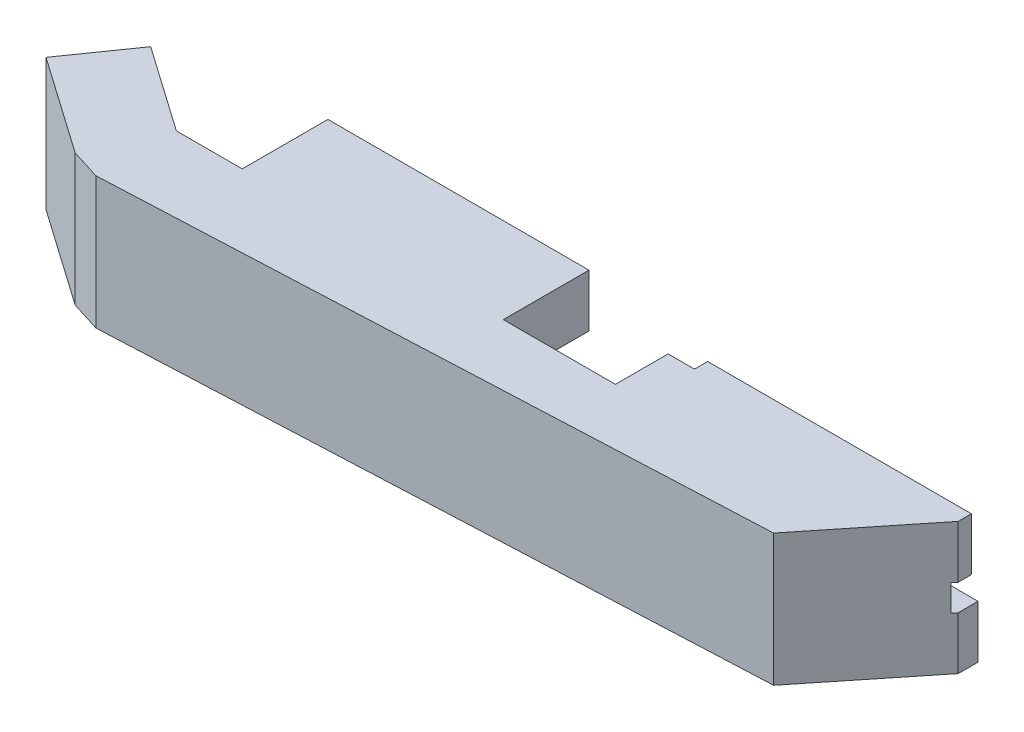
SolidWorks part; units mm, degrees
ref_plane "Front Plane" through (0, 0, 0) normal (0, 0, 1) x (1, 0, 0)
ref_plane "Top Plane" through (0, 0, 0) normal (0, 1, 0) x (1, 0, 0)
ref_plane "Right Plane" through (0, 0, 0) normal (1, 0, 0) x (0, 0, -1)
sketch "Sketch1" plane through (0, 0, 0) normal (0, 1, 0) x (1, 0, 0)
  line L0 (10.2515, 0) -> (39.2515, 0)
  line L1 (39.2515, 6) -> (47.2515, 6)
  line L6 (-8.1485, 0) -> (-15.5209, 5.1622)
  line L7 (-15.5209, 5.1622) -> (-15.693, 4.9164)
  line L11 (-0.0485, 0) -> (0.04, 0)
  line L12 (-8.1485, -0.3) -> (-8.2431, -0.3)
  line L13 (-15.693, 4.9164) -> (-8.2431, -0.3)
  line L14 (-8.1485, 0) -> (-8.245, -0.2987)
  line L18 (-15.693, 4.9164) -> (-14.5458, 6.5547)
  line L23 (-8.1485, 0) -> (-8.3206, -0.2457)
  line L24 (-14.5458, 6.5547) -> (-8.041, 2)
  line L25 (16.7515, 2) -> (25.2515, 2)
  line L26 (-3.0485, 2) -> (-8.041, 2)
  line L27 (-8.1485, 0) -> (-10.4428, -3.2766)
  line L28 (-15.5209, 5.1622) -> (-17.8152, 1.8856)
  line L29 (0.1927, 0) -> (10.0102, 0)
  line L30 (-0.0485, 0) -> (-3.0485, 0)
  line L31 (-3.0485, 2) -> (-3.0485, 8.5)
  line L32 (10.2515, 0) -> (16.7515, 0)
  line L33 (16.7515, 2) -> (16.7515, 8.5)
  line L34 (-3.0485, 8.5) -> (16.7515, 8.5)
  line L35 (27.2515, 6) -> (25.2515, 6)
  line L36 (25.2515, 6) -> (25.2515, 2)
  line L37 (39.0515, -0.3) -> (39.2515, -0.3)
  line L38 (39.2515, 0) -> (27.2515, 0)
  line L39 (47.2515, 6) -> (47.2515, 7)
  line L40 (47.2515, 7) -> (27.2515, 7)
  line L41 (-10.4428, -3.2766) -> (-17.8152, 1.8856)
  line L42 (27.2515, 6) -> (27.2515, 7)
  line L43 (-8.1485, 0) -> (-8.1485, -4)
  line L47 (-10.4428, -3.2766) -> (-8.1485, -4)
  line L48 (39.2515, 0) -> (41.0192, -1.7678)
  line L49 (-8.1485, -4) -> (41.0192, -1.7678)
  line L51 (41.0192, -1.7678) -> (47.2515, 6)
  line L56 (0.1927, -0.3) -> (0.1927, 0.6071)
  line L57 (-0.0073, -0.3) -> (0.1927, -0.3)
  line L58 (10.0102, -0.3) -> (10.0102, 0.6071)
  line L62 (47.0108, 5.7) -> (41.1339, 5.7)
  line L63 (10.2102, -0.3) -> (10.0102, -0.3)
  line L64 (41.7636, 3.4879) -> (40.1372, 5.1142)
  line L65 (41.5515, 3.7) -> (40.1372, 5.1142)
  line L66 (41.5515, 3.7) -> (41.7636, 3.4879)
  line L68 (39.2515, -0.3) -> (39.5515, -0.3)
  line L69 (39.5515, 0) -> (39.5515, -0.3)
  line L70 (39.5515, 0) -> (39.5515, 4.1175)
  line L71 (39.2515, 0) -> (39.5515, 0)
  line L81 (-8.1485, 0) -> (-8.1485, -0.3)
  line L83 (39.2515, 0) -> (39.2515, -0.3)
  line L86 (10.2102, 0) -> (10.1629, 0)
  line L87 (39.0515, -0.3) -> (-8.1485, -0.3)
  line L92 (39.2515, 0) -> (39.2515, -0.3)
  line L98 (5.1015, 0) -> (5.1015, -0.65)
  line L100 (-8.1485, 0) -> (-15.5209, 5.1622)
  line L101 (-0.0485, 0) -> (-8.1485, 0)
  line L102 (10.2515, 0) -> (10.2102, 0)
  line L104 (5.1015, 4.4993) -> (5.1015, 4.1993)
  line L105 (-0.0073, 0) -> (-0.0485, 0)
  line L106 (39.2515, 6) -> (39.2515, 3.7)
  line L107 (39.2515, 6) -> (41.5515, 6)
  line L108 (39.2515, 6) -> (47.2515, 6)
  line L109 (39.2515, 0) -> (39.2515, 6)
  arc A4 (39.5515, 4.1175) -> (41.1339, 5.7) centre (41.7636, 3.4879) cw
  arc A5 (-0.0073, -0.3) -> (10.2102, -0.3) centre (5.1015, -0.9507) cw
  arc A6 (-0.0073, 0) -> (10.2102, 0) centre (5.1015, -0.6507) cw
  arc A7 (39.2515, 3.7) -> (41.5515, 6) centre (41.5515, 3.7) cw
  dimension "D1" = 29
  dimension "D2" = 8
  dimension "D3" = 9
  dimension "D4" = 145
  dimension "D5" = 90
  dimension "D6" = 90
  dimension "D7" = 2
  dimension "D8" = 3
  dimension "D9" = 8.5
  dimension "D10" = 6.5
  dimension "D11" = 14
  dimension "D12" = 12
  dimension "D13" = 1
  dimension "D14" = 4
  dimension "D15" = 90
  dimension "D16" = 90
  dimension "D17" = 4
  dimension "D18" = 2.5
extrude "Boss-Extrude1" add sketch "Sketch1" along normal blind 4 contours L11 A6 L102 L0 L109 L106 L1 L39 L40 L42 L35 L36 L25 L33 L34 L31 L26 L24 L18 L6 L101 L30 | A5 L56 L29 L58 | A6 L11 A5 L104 | A6 L104 A5 L86 | A5 L57 L56 | L98 L29 L56 L87 | A5 L58 L63 | L29 L98 L87 L58 | L86 A5 L87 L37 L83 L0 L102 | L37 L87 L63 L57 L43 L49 L48 L68 | L106 A7 L1 | A7 L109 L71 L70 A4 L62 L51 L1 | L71 L48 L69 | L48 L83 L68 | L41 L27 L13 L28 | L23 L6 L7 L13 | L27 L47 L43 L12 L13 | L14 L23 L13 | L43 L14 L13 L12 | L87 A5 L11 L30 L101 L43 region at (16.3657, 0, -3.9715) region at (24.7198, 0, 0.15) region at (10.1866, 0, -0.0681) region at (10.0821, 0, -0.0216) region at (5.0334, 0, -4.3493) region at (39.4515, 0, 0.1) region at (39.3515, 0, -1.85) region at (39.3515, 0, 0.2) region at (5.1015, 0, -1.7619) region at (12.6593, 0, 1.6798) region at (-4.0668, 0, 0.1499) region at (39.7652, 0, -5.4863) region at (7.5558, 0, 0.15) region at (0.1209, 0, -0.0216) region at (2.6471, 0, 0.15) region at (-8.9177, 0, 2.4394) region at (-11.9208, 0, -2.4582) region at (-8.1808, 0, 0.2) region at (-8.238, 0, 0.1815) region at (-13.0679, 0, -0.8199)
extrude "Boss-Extrude3" add sketch "Sketch1<7>" against normal blind 2 contours L37 L87 L63 L57 L43 L49 L48 L68 | L27 L47 L43 L12 L13 | L41 L27 L13 L28 | A5 L56 L29 L58 | L98 L29 L56 L87 | L29 L98 L87 L58 region at (5.1015, 0, -1.7619) region at (12.6593, 0, 1.6798) region at (7.5558, 0, 0.15) region at (2.6471, 0, 0.15) region at (-8.9177, 0, 2.4394) region at (-13.0679, 0, -0.8199)
sketch "Sketch1<7>" plane through (0, 0, 0) normal (0, 1, 0) x (1, 0, 0) same geometry as "Sketch1"
ref_plane "Plane1" through (0, -2, 0) normal (0, -1, 0) x (-1, 0, 0)
sketch "Sketch2" plane through (0, -2, 0) normal (0, -1, 0) x (-1, 0, 0)
  line L0 (-47.2515, 6) -> (-47.2515, 7.5)
  line L6 (-47.2515, 7.5) -> (-37.2142, 7.5)
  line L7 (-37.2142, 7.5) -> (-33.2515, 7.5)
  line L12 (-33.2515, 4.5) -> (-33.2515, 7.5)
  line L13 (-24.7515, 4.5) -> (-24.7515, 7.5)
  line L14 (-24.7515, 7.5) -> (3.0485, 7.5)
  line L18 (-28.6383, 4.5) -> (-33.2515, 4.5)
  line L23 (-28.6383, 4.5) -> (-24.7515, 4.5)
  line L25 (2.5485, 1.5) -> (2.5485, 7.5)
  line L27 (6.8039, 1.5) -> (2.5485, 1.5)
  line L30 (9.4059, 3.3219) -> (6.8039, 1.5)
  line L31 (9.4059, 3.3219) -> (14.3738, 6.8005)
  line L32 (14.5458, 6.5547) -> (14.3738, 6.8005)
  line L33 (-16.7515, 7.5) -> (-16.7515, 8.5)
  line L97 (-41.0192, -1.7678) -> (-47.2515, 6)
  line L99 (8.1485, -4) -> (-41.0192, -1.7678)
  line L110 (10.4428, -3.2766) -> (8.1485, -4)
  line L113 (10.4428, -3.2766) -> (17.8152, 1.8856)
  line L115 (-47.2515, 6) -> (-47.2515, 7)
  line L122 (3.0485, 2) -> (3.0485, 7.5)
  line L125 (15.5209, 5.1622) -> (17.8152, 1.8856)
  line L127 (3.0485, 2) -> (7.5179, 2)
  line L131 (15.693, 4.9164) -> (14.5458, 6.5547)
  line L136 (15.5209, 5.1622) -> (15.693, 4.9164)
  dimension "D1" = 1.5
extrude "Boss-Extrude4" add sketch "Sketch1<8>" along normal blind 4 contours A4 L70 L69 L48 L51 L62 region at (42.2448, 0, -2.8774)
sketch "Sketch1<8>" plane through (0, 0, 0) normal (0, 1, 0) x (1, 0, 0) same geometry as "Sketch1"
extrude "Boss-Extrude5" add sketch "Sketch1<9>" against normal blind 2 contours A4 L70 L69 L48 L51 L62 region at (42.2448, 0, -2.8774)
sketch "Sketch1<9>" plane through (0, 0, 0) normal (0, 1, 0) x (1, 0, 0) same geometry as "Sketch1"
extrude "Boss-Extrude6" add sketch "Sketch2" along normal blind 4 contours L125 L131 L32 L31 L30 L27 L25 L14 L13 L23 L18 L12 L7 L6 L0 L97 L99 L110 L113 region at (14.9815, -2, -2.0133)
